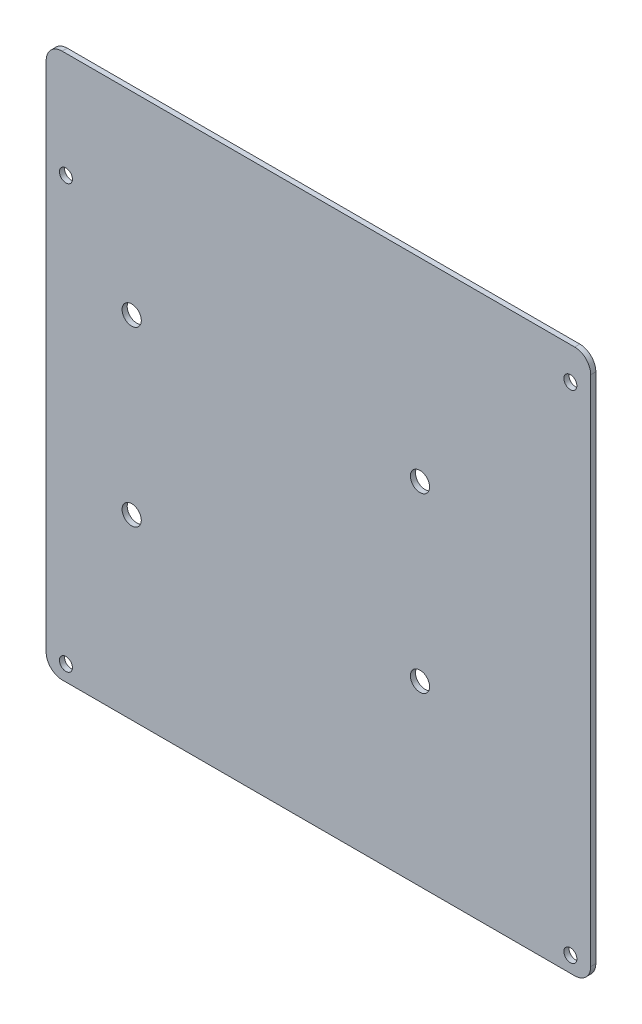
SolidWorks part; units mm, degrees
material "Epoxy, Unfilled"
ref_plane "Front Plane" through (0, 0, 0) normal (0, 0, 1) x (1, 0, 0)
ref_plane "Top Plane" through (0, 0, 0) normal (0, 1, 0) x (1, 0, 0)
ref_plane "Right Plane" through (0, 0, 0) normal (1, 0, 0) x (0, 0, -1)
sketch "Sketch1" plane through (0, 0, 0) normal (0, 0, 1) x (1, 0, 0)
  line L1 (85, -85) -> (-85, -85)
  line L2 (85, -85) -> (85, 85)
  line L3 (85, 85) -> (-85, 85)
  line L4 (-85, -85) -> (-85, 85)
  line L5 (85, -85) -> (-85, 85) construction
  line L6 (85, 85) -> (-85, -85) construction
  point P0 (0, 0)
  dimension "D1" = 170
  dimension "D2" = 170
extrude "Base" add sketch "Sketch1" along normal blind 1.6
fillet "Rounding corners" radius 5 4 edges at (-85, 85, 0.8) (85, 85, 0.8) (85, -85, 0.8) (-85, -85, 0.8)
sketch "Sketch2" plane through (0, 0, 1.6) normal (0, 0, 1) x (1, 0, 0)
  line L0 (85, -80) -> (85, 80) construction
  line L1 (80, 85) -> (-80, 85) construction
  circle A0 centre (-78.83, 51.98) radius 2.03
  circle A1 centre (78.65, 74.84) radius 2.03
  circle A2 centre (-78.83, -80.1) radius 2.03
  circle A3 centre (78.65, -80.1) radius 2.03
  point P12 (0, 0)
  dimension "D1" = 4.06
  dimension "D2" = 4.06
  dimension "D3" = 4.06
  dimension "D4" = 4.06
  dimension "D5" = 157.48
  dimension "D6" = 22.86
  dimension "D7" = 6.35
  dimension "D8" = 10.16
  dimension "D9" = 154.94
  dimension "D10" = 6.35
  dimension "D11" = 157.48
  dimension "D12" = 0
extrude "Mounting holes" cut sketch "Sketch2" against normal blind 1.6
sketch "Sketch4" plane through (0, 0, 1.6) normal (0, 0, 1) x (1, 0, 0)
  line L0 (-85, 80) -> (-85, -80) construction
  line L1 (-80, -85) -> (80, -85) construction
  circle A0 centre (-58.3, 24.5) radius 3
  circle A1 centre (31.7, 24.5) radius 3
  circle A2 centre (31.7, -29.5) radius 3
  circle A3 centre (-58.3, -29.5) radius 3
  point P12 (-51.1379, -48.724)
  dimension "D1" = 6
  dimension "D2" = 6
  dimension "D3" = 6
  dimension "D4" = 6
  dimension "D5" = 90
  dimension "D6" = 26.7
  dimension "D7" = 54
  dimension "D8" = 26.7
  dimension "D9" = 55.5
  dimension "D10" = 90
  dimension "D11" = 54
  dimension "D12" = 55.5
extrude "Cooler holes" cut sketch "Sketch4" against normal blind 1.6
